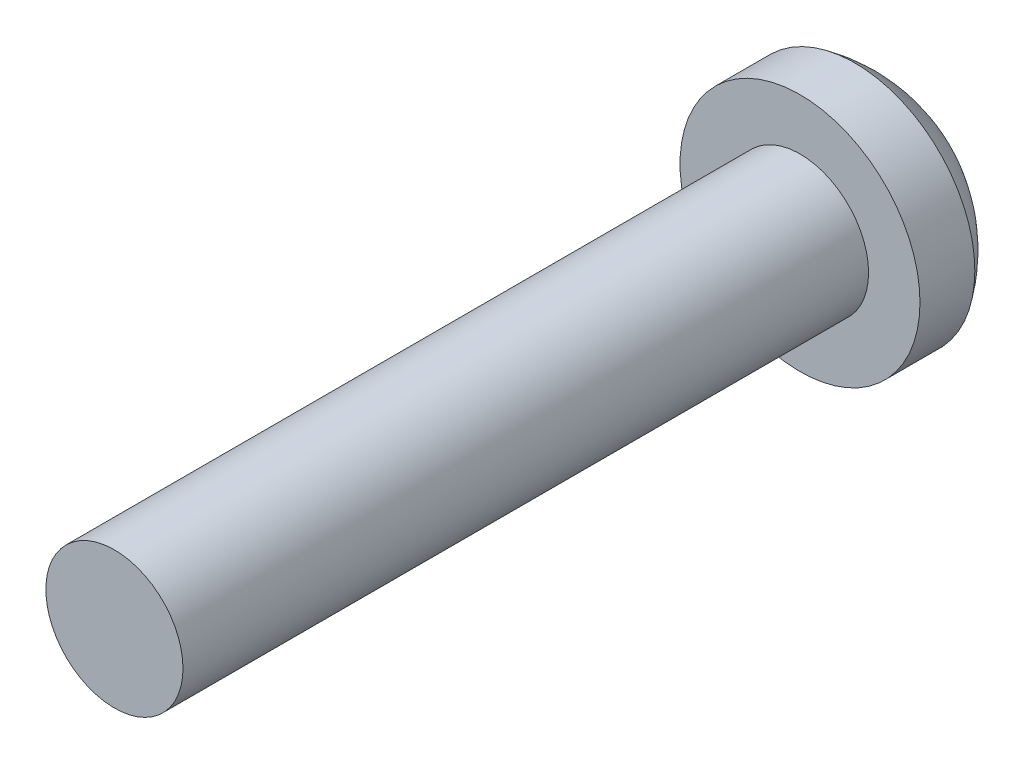
SolidWorks part; units mm, degrees
ref_plane "Front Plane" through (0, 0, 0) normal (0, 0, 1) x (1, 0, 0)
ref_plane "Top Plane" through (0, 0, 0) normal (0, 1, 0) x (1, 0, 0)
ref_plane "Right Plane" through (0, 0, 0) normal (1, 0, 0) x (0, 0, -1)
sketch "Sketch1" plane through (0, 0, 0) normal (0, 1, 0) x (1, 0, 0)
  line L0 (0, -117.2331) -> (0, 5744.4225) construction
  line L1 (0, 0) -> (1, 0)
  line L2 (1, 0) -> (1, 10)
  line L3 (1, 10) -> (1.75, 10)
  line L4 (1.75, 10) -> (1.75, 10.8)
  line L7 (0, 11.7122) -> (0, 0)
  arc A3 (1.75, 10.8) -> (0, 11.7122) centre (0, 9.5776) ccw
  point P10 (0, 10)
  dimension "D1" = 2.1347
  dimension "D2" = 1
  dimension "D3" = 10
  dimension "D4" = 0.75
  dimension "D5" = 0.8
revolve "Revolve1" add sketch "Sketch1" angle 360 about L0
sketch3d "3DSketch2" plane through (0, 0, 0) normal (0, 0, 1) x (1, 0, 0)
  dimension "D1" = 11.7
sketch "Sketch2" plane through (0, 0, -11.7) normal (0, 0, 1) x (1, 0, 0)
  line L0 (-1000, 0) -> (49000, 0) construction
  line L1 (0, -1000) -> (0, 49000) construction
  line L2 (-0.25, 1.188) -> (-0.25, 0.25)
  line L3 (0.25, 1.188) -> (0.25, 0.25)
  line L4 (1.188, 0.25) -> (0.25, 0.25)
  line L5 (1.188, -0.25) -> (0.25, -0.25)
  line L6 (0.25, -1.188) -> (0.25, -0.25)
  line L7 (-0.25, -1.188) -> (-0.25, -0.25)
  line L8 (-1.188, -0.25) -> (-0.25, -0.25)
  line L9 (-1.188, 0.25) -> (-0.25, 0.25)
  arc A0 (0.25, 1.188) -> (-0.25, 1.188) centre (0, 0) ccw
  circle A1 centre (0, 0) radius 1.214 construction
  arc A2 (1.188, -0.25) -> (1.188, 0.25) centre (0, 0) ccw
  arc A3 (-0.25, -1.188) -> (0.25, -1.188) centre (0, 0) ccw
  arc A4 (-1.188, 0.25) -> (-1.188, -0.25) centre (0, 0) ccw
  point P26 (0, 0)
  dimension "D3" = 2.428
  dimension "D1" = 0.5
  dimension "D2" = 4
extrude "Cut-Extrude1" cut sketch "Sketch2" against normal mid plane 1
